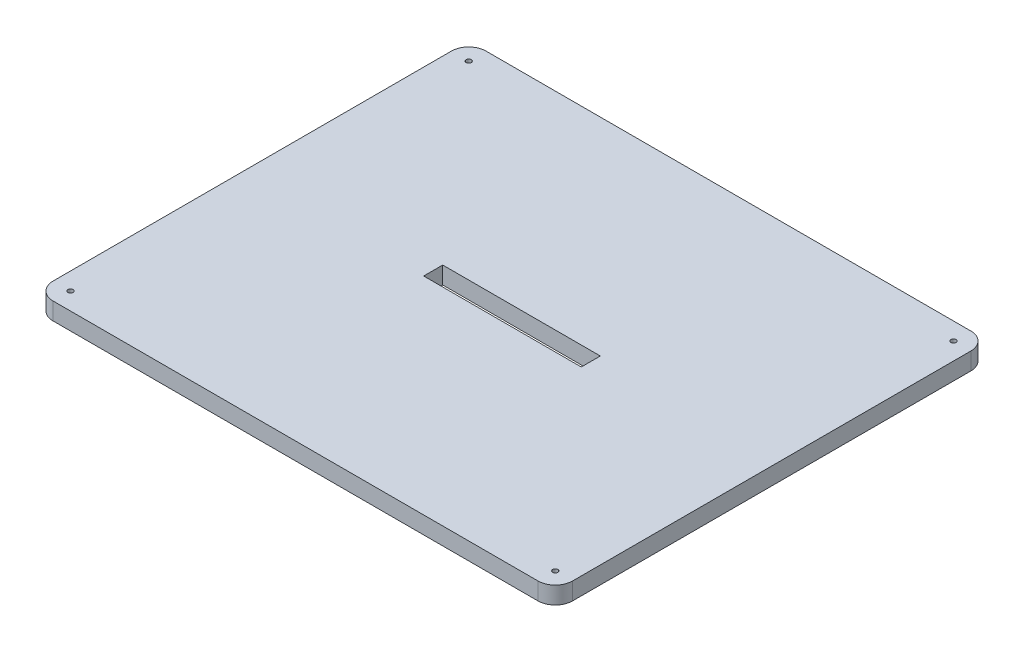
SolidWorks part; units mm, degrees
ref_plane "Спереди" through (0, 0, 0) normal (0, 0, 1) x (1, 0, 0)
ref_plane "Сверху" through (0, 0, 0) normal (0, 1, 0) x (1, 0, 0)
ref_plane "Справа" through (0, 0, 0) normal (1, 0, 0) x (0, 0, -1)
sketch "Эскиз1" plane through (0, 0, 0) normal (0, 1, 0) x (1, 0, 0)
  line L1 (150, -125) -> (-150, -125)
  line L2 (150, -125) -> (150, 125)
  line L3 (150, 125) -> (-150, 125)
  line L4 (-150, -125) -> (-150, 125)
  line L5 (150, -125) -> (-150, 125) construction
  line L6 (150, 125) -> (-150, -125) construction
  point P0 (0, 0)
  dimension "D1" = 250
  dimension "D2" = 300
extrude "Бобышка-Вытянуть1" add sketch "Эскиз1" along normal mid plane 10
fillet "Скругление1" radius 10 4 edges at (-150, 0, -125) (150, 0, -125) (150, 0, 125) (-150, 0, 125)
sketch "Эскиз2" plane through (0, 5, 0) normal (0, 1, 0) x (1, 0, 0)
  line L0 (0, 0) -> (0, -33.246) construction
  line L1 (0, 0) -> (-47.6996, 0) construction
  circle A0 centre (-140, 115) radius 1.5
  circle A1 centre (-140, -115) radius 1.5
  circle A2 centre (140, -115) radius 1.5
  circle A3 centre (140, 115) radius 1.5
extrude "Вырез-Вытянуть1" cut sketch "Эскиз2" against normal up to surface (10 mm away) up to face at (0, -5, 0)
sketch "Эскиз3" plane through (0, 5, 0) normal (0, 1, 0) x (1, 0, 0)
  line L1 (45.5, -5.5) -> (-45.5, -5.5)
  line L2 (45.5, -5.5) -> (45.5, 5.5)
  line L3 (45.5, 5.5) -> (-45.5, 5.5)
  line L4 (-45.5, -5.5) -> (-45.5, 5.5)
  line L5 (45.5, -5.5) -> (-45.5, 5.5) construction
  line L6 (45.5, 5.5) -> (-45.5, -5.5) construction
  point P0 (0, 0)
  dimension "D1" = 11
  dimension "D2" = 91
extrude "Вырез-Вытянуть2" cut sketch "Эскиз3" against normal up to surface (10 mm away) up to face at (140, -5, -113.5)
